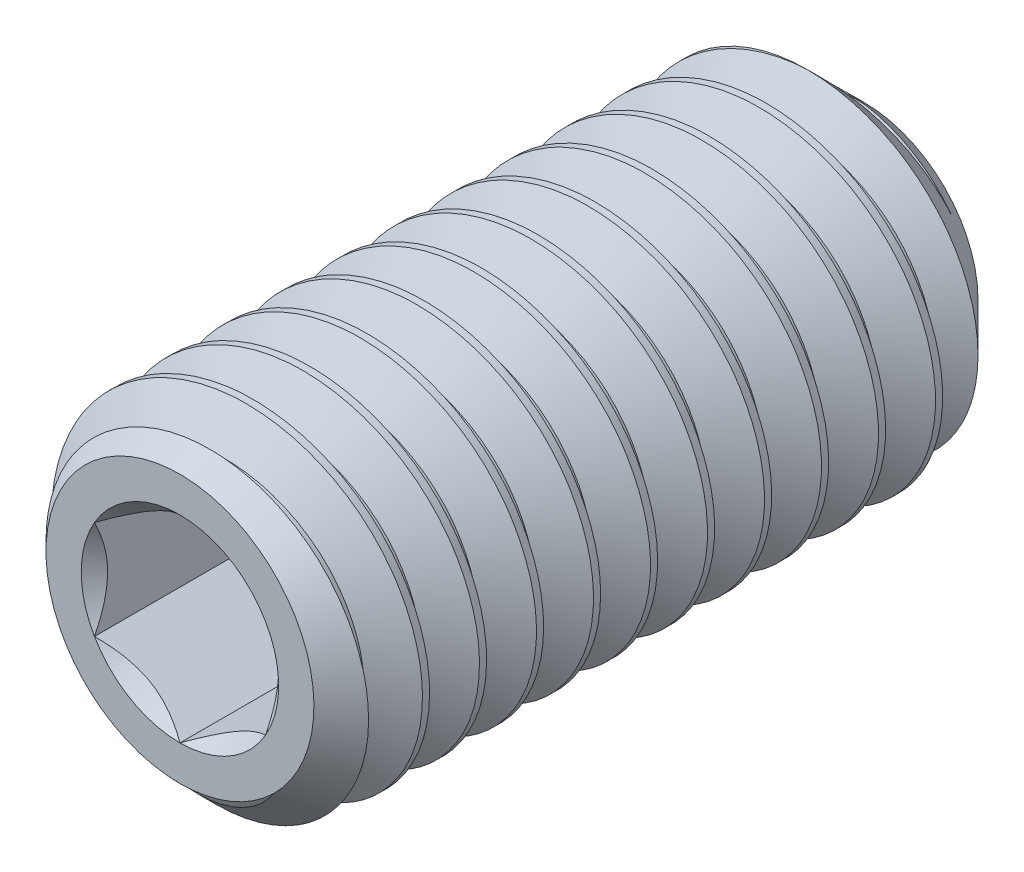
SolidWorks part; units mm, degrees
ref_plane "Front Plane" through (0, 0, 0) normal (0, 0, 1) x (1, 0, 0)
ref_plane "Top Plane" through (0, 0, 0) normal (0, 1, 0) x (1, 0, 0)
ref_plane "Right Plane" through (0, 0, 0) normal (1, 0, 0) x (0, 0, -1)
sketch "Sketch1" plane through (0, 0, 0) normal (1, 0, 0) x (0, 0, -1)
  line L0 (-3, 0) -> (3, 0) construction
  line L1 (-3, -1.5) -> (-3, 1.5) construction
  line L2 (-3, -0.75) -> (-3, 0.75) construction
  line L3 (-3, 1.5) -> (3, 1.5) construction
  line L4 (3, 1.5) -> (3, 0) construction
  line L5 (-3.4688, 1.5541) -> (-2.9688, 1.5541)
  line L6 (-2.9688, 1.5541) -> (-3.2188, 1.1211)
  line L7 (-3.2188, 1.1211) -> (-3.4688, 1.5541)
  line L8 (-3.2188, 1.1211) -> (-3.2188, 1.1752)
  line L9 (-3.2188, 1.5541) -> (-3.2188, 1.5)
  line L10 (-3.4375, 1.5) -> (-3, 1.5)
  line L11 (-3.4531, 1.5271) -> (-2.9844, 1.5271)
  line L12 (-3.25, 1.1752) -> (-3.1875, 1.1752)
  line L13 (-3, 1.1752) -> (-2.6752, 1.5) construction
  line L14 (-3, -1.1752) -> (-2.6752, -1.5) construction
  line L15 (2.5, 1.5) -> (3, 1) construction
  point P3 (-2.25, -1.5)
  point P4 (0, 0)
  point P8 (-3, 0)
  point P11 (-3, 0)
  point P18 (-1, 0)
  point P21 (-3.2188, 1.5)
  point P24 (-3.2188, 1.5271)
  point P27 (-3.2188, 1.1752)
  dimension "Length" = 6
  dimension "Thread Size" = 3
  dimension "Drive Size" = 1.5
  dimension "Thread Pitch" = 0.5
  dimension "D1" = 0.0625
  dimension "D2" = 0.75
  dimension "Drive Depth" = 2
  dimension "Drive Side Chamfer Angle" = 90
  dimension "Bottom Chamfer Angle" = 45
  dimension "Bottom Chamfer Diameter" = 2
sketch "Sketch2" plane through (0, 0, 0) normal (1, 0, 0) x (0, 0, -1)
  line L0 (2.5, 1.5) -> (3, 1) construction
  line L1 (-3, 0) -> (3, 0)
  line L2 (-3, 0) -> (-3, 1.1752)
  line L3 (-2.6752, 1.5) -> (2.5, 1.5)
  line L4 (3, 0) -> (3, 1)
  line L5 (-3, 1.1752) -> (-2.6752, 1.5) construction
  line L6 (2.5, 1.5) -> (3, 1)
  line L7 (-3, 1.1752) -> (-2.6752, 1.5)
revolve "Revolve1" add sketch "Sketch2" angle 360 about L1
sketch "Sketch3" plane through (0, 0, 3) normal (0, 0, 1) x (1, 0, 0)
  line L0 (0, -0.75) -> (0, 0.75) construction
  line L1 (0, 0.866) -> (-0.75, 0.433)
  line L2 (-0.75, 0.433) -> (-0.75, -0.433)
  line L3 (-0.75, -0.433) -> (0, -0.866)
  line L4 (0, -0.866) -> (0.75, -0.433)
  line L5 (0.75, -0.433) -> (0.75, 0.433)
  line L6 (0.75, 0.433) -> (0, 0.866)
  line L7 (0, -1.5) -> (0, 1.5) construction
  circle A0 centre (0, 0) radius 0.75 construction
extrude "Cut-Extrude1" cut sketch "Sketch3" against normal up to vertex (3 mm away) up to point (0, 0, 0)
sketch "Sketch4" plane through (0, 0, 0) normal (0, 0, 1) x (1, 0, 0)
  line L0 (-0.75, 0.433) -> (-0.75, -0.433) construction
  circle A0 centre (0, 0) radius 0.75
extrude "Cut-Extrude2" cut sketch "Sketch4" against normal through all draft 60
sketch "Sketch5" plane through (0, 0, 3) normal (0, 0, 1) x (1, 0, 0)
  line L0 (0, -1.5) -> (0, 1.5) construction
  circle A0 centre (0, 0) radius 0.866
extrude "Cut-Extrude3" cut sketch "Sketch5" against normal blind 2 draft 45
sketch "Sketch6" plane through (0, 0, 3) normal (0, 0, 1) x (1, 0, 0)
  line L0 (0, -1.5) -> (0, 1.5) construction
  circle A0 centre (0, 0) radius 1.5
curve "Helix/Spiral1" pitch 0.5 height 6.5 radius 1.5 centre (0, 0, 3) axis (0, 0, -1) start towards (0, 1, 0)
sketch "Sketch7" plane through (0, 0, 0) normal (1, 0, 0) x (0, 0, -1)
  line L0 (-3.4531, 1.5271) -> (-2.9844, 1.5271)
  line L1 (-2.9844, 1.5271) -> (-3.1875, 1.1752)
  line L2 (-3.1875, 1.1752) -> (-3.25, 1.1752)
  line L3 (-3.25, 1.1752) -> (-3.4531, 1.5271)
sweep "Cut-Sweep1" cut profiles "Sketch7" path "Helix/Spiral1"
equation "\"D1@Sketch1\"=\"Thread Pitch@Sketch1\"/8"
equation "\"D1\"= \"Length@Sketch1\" * .438"
equation "\"D4@Helix/Spiral1\"=\"Thread Pitch@Sketch1\""
equation "\"D3@Helix/Spiral1\"=\"Thread Pitch@Sketch1\"+\"Length@Sketch1\""
equation "\"D2@Sketch1\"=\"Thread Pitch@Sketch1\"*1.5"
equation "\"D1@Cut-Extrude3\"=\"Drive Depth@Sketch1\""
